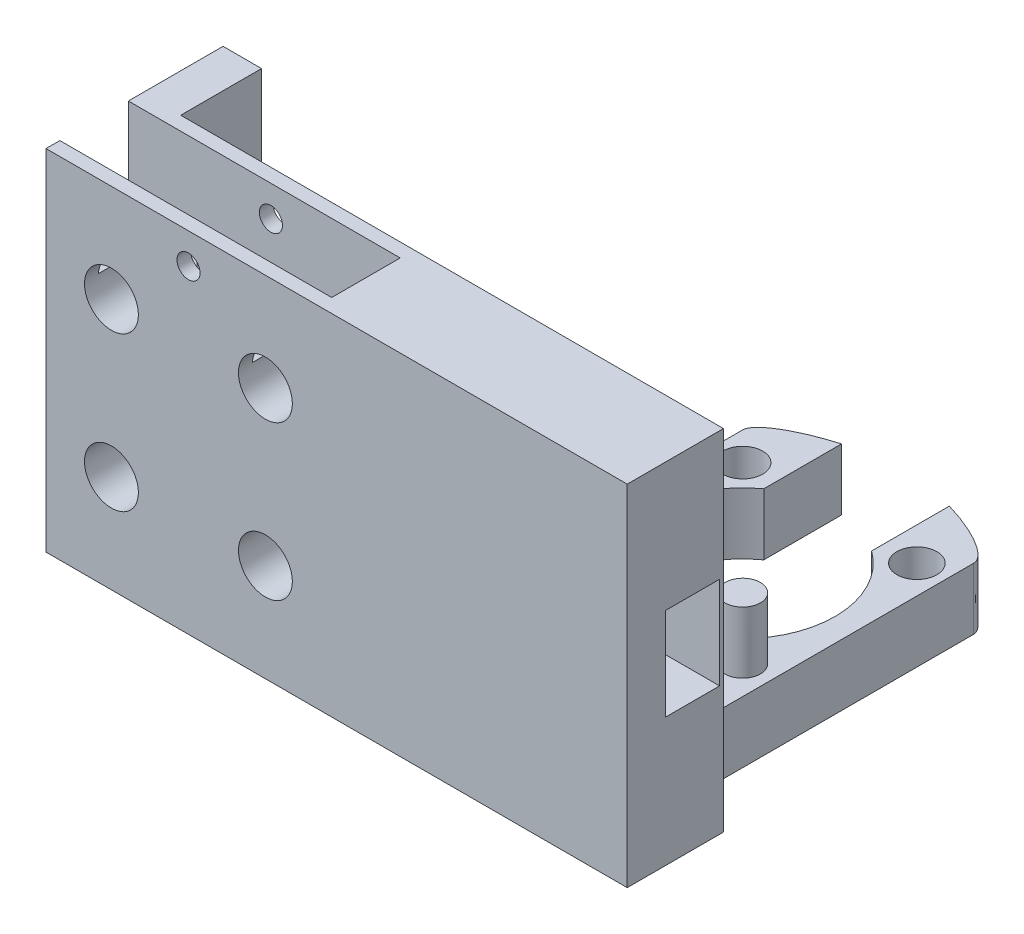
SolidWorks part; units mm, degrees
ref_plane "Front Plane" through (0, 0, 0) normal (0, 0, 1) x (1, 0, 0)
ref_plane "Top Plane" through (0, 0, 0) normal (0, 1, 0) x (1, 0, 0)
ref_plane "Right Plane" through (0, 0, 0) normal (1, 0, 0) x (0, 0, -1)
sketch "Sketch1" plane through (0, 0, 0) normal (0, 0, 1) x (1, 0, 0)
  line L1 (0, 0) -> (75.5, 0)
  line L2 (0, 0) -> (0, 45.4)
  line L3 (0, 45.4) -> (75.5, 45.4)
  line L4 (75.5, 0) -> (75.5, 45.4)
  line L5 (8.5, 32.7) -> (28.5, 32.7) construction
  line L6 (8.5, 32.7) -> (8.5, 12.7) construction
  line L7 (8.5, 12.7) -> (28.5, 12.7) construction
  line L8 (28.5, 32.7) -> (28.5, 12.7) construction
  circle A0 centre (8.5, 32.7) radius 1.65
  circle A1 centre (28.5, 32.7) radius 1.65
  circle A2 centre (28.5, 12.7) radius 1.65
  circle A3 centre (8.5, 12.7) radius 1.65
  dimension "D3" = 3.3
  dimension "D1" = 45.4
  dimension "D2" = 75.5
  dimension "D4" = 12.7
  dimension "D5" = 20
  dimension "D6" = 8.5
extrude "Boss-Extrude1" add sketch "Sketch1" along normal blind 12.5
sketch "Sketch2" plane through (0, 0, 0) normal (0, 0, -1) x (-1, 0, 0)
  line L0 (0, 0) -> (-75.5, 0) construction
  line L1 (0, 45.4) -> (-5, 45.4)
  line L2 (0, 45.4) -> (0, 0)
  line L3 (0, 0) -> (-5, 0)
  line L4 (-5, 45.4) -> (-5, 0)
  dimension "D1" = 5
extrude "Boss-Extrude2" add sketch "Sketch2" along normal blind 10.5
sketch "Sketch3" plane through (0, 0, 0) normal (0, 0, 1) x (1, 0, 0)
  line L0 (75.5, 0) -> (75.5, 45.4) construction
  line L1 (75.5, 28.7) -> (0, 28.7)
  line L2 (75.5, 28.7) -> (75.5, 16.7)
  line L3 (75.5, 16.7) -> (0, 16.7)
  line L4 (0, 28.7) -> (0, 16.7)
  line L5 (0, 0) -> (0, 45.4) construction
  line L6 (75.5, 22.7) -> (0, 22.7) construction
  point P10 (75.5, 22.7)
  dimension "D1" = 12
extrude "Cut-Extrude1" cut sketch "Sketch3" against normal through all and the other way blind 7.5
sketch "Sketch4" plane through (0, 0, 0) normal (0, 0, -1) x (-1, 0, 0)
  line L0 (-75.5, 28.7) -> (-75.5, 45.4) construction
  line L1 (-69.5, 0) -> (-39.5, 0)
  line L2 (-69.5, 0) -> (-69.5, 8)
  line L3 (-69.5, 8) -> (-39.5, 8)
  line L4 (-39.5, 0) -> (-39.5, 8)
  line L7 (-5, 0) -> (-75.5, 0) construction
  dimension "D1" = 8
  dimension "D2" = 30
  dimension "D3" = 6
extrude "Boss-Extrude3" add sketch "Sketch4" along normal blind 44.5
sketch "Sketch5" plane through (0, 8, 0) normal (0, 1, 0) x (1, 0, 0)
  line L0 (69.5, 44.5) -> (69.5, 0) construction
  line L1 (75.5, 0) -> (5, 0) construction
  circle A0 centre (54.4956, 23.5) radius 12
  dimension "D1" = 24
  dimension "D2" = 15.0044
  dimension "D3" = 23.5
extrude "Cut-Extrude2" cut sketch "Sketch5" against normal blind 45
sketch "Sketch6" plane through (0, 16.7, 0) normal (0, -1, 0) x (1, 0, 0)
  circle A3 centre (54.4956, -39.5013) radius 2.6
  circle A4 centre (65.8093, -34.815) radius 2.6
  circle A5 centre (43.1819, -34.815) radius 2.6
  dimension "D1" = 5.2
extrude "Cut-Extrude3" cut sketch "Sketch6" against normal through all both and the other way through all
fillet "Fillet1" radius 6 2 edges at (39.5, 4, -44.5) (69.5, 4, -44.5) second distance 15 conic rho 0.3 first distance on face at (39.5, 4, -22.25) first distance on face at (69.5, 4, -22.25)
ref_plane "Plane1" through (0, 0, 10.7) normal (0, 0, 1) x (1, 0, 0)
sketch "Sketch8" plane through (0, 0, 12.5) normal (0, 0, 1) x (1, 0, 0)
  circle A0 centre (8.5, 32.7) radius 3.5
  circle A1 centre (28.5, 32.7) radius 3.5
  circle A2 centre (8.5, 12.7) radius 3.5
  circle A3 centre (28.5, 12.7) radius 3.5
  dimension "D1" = 7
extrude "Cut-Extrude5" cut sketch "Sketch8" against normal offset from surface (9.5 mm away) 3 up to face at (10.15, 32.7, 0)
sketch "Sketch12" plane through (0, 0, 10.7) normal (0, 0, 1) x (1, 0, 0)
  line L5 (-10.6174, 50.6437) -> (35.3137, 50.6437)
  line L6 (-10.6174, 50.6437) -> (-10.6174, 32.9343)
  line L7 (-10.6174, 32.9343) -> (35.3137, 32.9343)
  line L8 (35.3137, 50.6437) -> (35.3137, 32.9343)
extrude "Cut-Extrude8" cut sketch "Sketch12" against normal offset from surface (8.9 mm away) 1.8 up to face at (10.15, 32.7, 0)
sketch "Sketch11" plane through (0, 0, 10.7) normal (0, 0, 1) x (1, 0, 0)
  circle A0 centre (18.5132, 41.4) radius 1.5
  dimension "D1" = 3
extrude "Cut-Extrude9" cut sketch "Sketch11" against normal through all both and the other way through all
sketch "Sketch13" plane through (0, 8, 0) normal (0, 1, 0) x (1, 0, 0)
  line L1 (61.4956, 51.1384) -> (47.4956, 51.1384)
  line L2 (61.4956, 51.1384) -> (61.4956, 27.8643)
  line L3 (61.4956, 27.8643) -> (47.4956, 27.8643)
  line L4 (47.4956, 51.1384) -> (47.4956, 27.8643)
  line L5 (61.4956, 51.1384) -> (47.4956, 27.8643) construction
  line L6 (61.4956, 27.8643) -> (47.4956, 51.1384) construction
  point P0 (54.4956, 39.5013)
  dimension "D1" = 14
extrude "Cut-Extrude10" cut sketch "Sketch13" against normal blind 10
sketch "Sketch14" plane through (0, 0, 0) normal (0, 0, -1) x (-1, 0, 0)
  line L1 (-75.5, 28.7) -> (0, 28.7)
  line L2 (-75.5, 28.7) -> (-75.5, 16.7)
  line L3 (-75.5, 16.7) -> (0, 16.7)
  line L4 (0, 28.7) -> (0, 16.7)
extrude "Boss-Extrude5" add sketch "Sketch14" against normal blind 0.5
sketch "Sketch15" plane through (0, 8, 0) normal (0, 1, 0) x (1, 0, 0)
  circle A0 centre (54.4956, 7.5013) radius 2.3
  circle A1 centre (65.8093, 12.1876) radius 2.3
  circle A2 centre (43.1819, 12.1876) radius 2.3
  dimension "D1" = 4.6
extrude "Boss-Extrude6" add sketch "Sketch15" along normal blind 8
